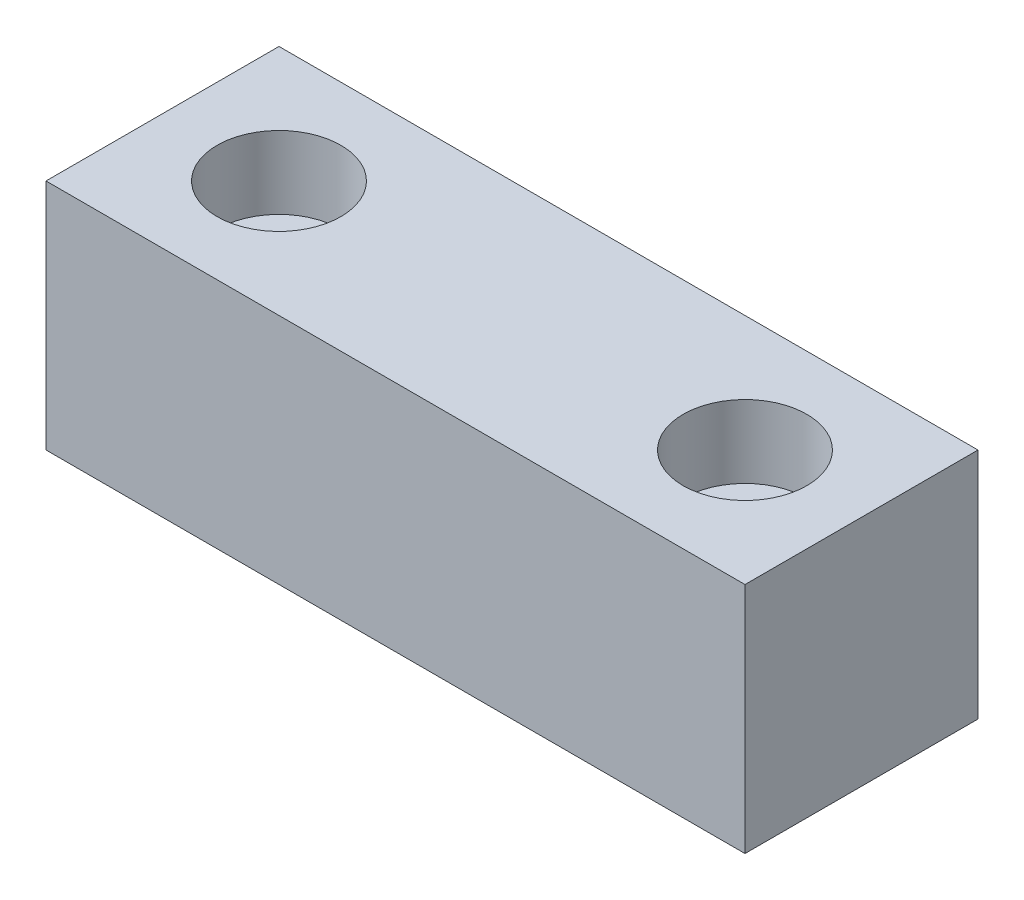
SolidWorks part; units mm, degrees
ref_plane "Front Plane" through (0, 0, 0) normal (0, 0, 1) x (1, 0, 0)
ref_plane "Top Plane" through (0, 0, 0) normal (0, 1, 0) x (1, 0, 0)
ref_plane "Right Plane" through (0, 0, 0) normal (1, 0, 0) x (0, 0, -1)
sketch "Sketch1" plane through (0, 0, 0) normal (0, 1, 0) x (1, 0, 0)
  line L1 (-38.1, -12.7) -> (38.1, -12.7)
  line L2 (-38.1, -12.7) -> (-38.1, 12.7)
  line L3 (-38.1, 12.7) -> (38.1, 12.7)
  line L4 (38.1, -12.7) -> (38.1, 12.7)
  line L5 (-38.1, -12.7) -> (38.1, 12.7) construction
  line L6 (-38.1, 12.7) -> (38.1, -12.7) construction
  point P0 (0, 0)
  dimension "D1" = 38.1
  dimension "D2" = 12.7
extrude "Boss-Extrude1" add sketch "Sketch1" along normal mid plane 25.4
sketch "Sketch2" plane through (0, 0, 0) normal (0, 1, 0) x (1, 0, 0)
  circle A0 centre (-25.4, 0) radius 4.3688
  circle A1 centre (25.4, 0) radius 4.3688
  point P4 (0, 0)
  dimension "D1" = 8.7376
  dimension "D2" = 8.7376
  dimension "D3" = 50.8
  dimension "D4" = 25.4
extrude "Cut-Extrude2" cut sketch "Sketch2" against normal blind 76.2 from offset 12.7
sketch "Sketch3" plane through (0, 0, 0) normal (0, 1, 0) x (1, 0, 0)
  circle A0 centre (-25.4, 0) radius 6.7437
  circle A1 centre (25.4, 0) radius 6.7437
  point P4 (0, 0)
  dimension "D1" = 13.4874
  dimension "D2" = 13.4874
  dimension "D3" = 50.8
  dimension "D4" = 25.4
extrude "Cut-Extrude4" cut sketch "Sketch3" against normal blind 7.9248 from offset 12.7
